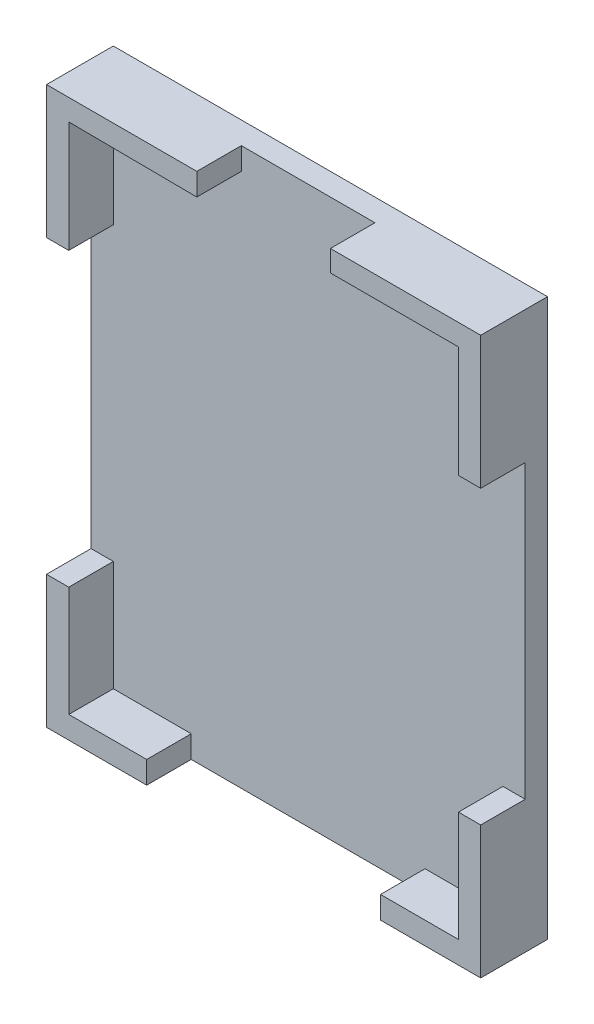
SolidWorks part; units mm, degrees
ref_plane "Front Plane" through (0, 0, 0) normal (0, 0, 1) x (1, 0, 0)
ref_plane "Top Plane" through (0, 0, 0) normal (0, 1, 0) x (1, 0, 0)
ref_plane "Right Plane" through (0, 0, 0) normal (1, 0, 0) x (0, 0, -1)
sketch "Sketch1" plane through (0, 0, 0) normal (0, 0, 1) x (1, 0, 0)
  line L5 (0, 50) -> (13.5, 50)
  line L8 (13.5, 50) -> (13.5, 48)
  line L9 (2, 48.0947) -> (13.5, 48)
  line L14 (37, 2) -> (30, 2)
  line L19 (37, 48.0947) -> (37, 38.0947)
  line L20 (39, 38.0947) -> (37, 38.0947)
  line L21 (39, 50) -> (39, 38.0947)
  line L22 (39, 0) -> (39, 11.9053)
  line L23 (39, 11.9053) -> (37, 11.9053)
  line L24 (37, 2) -> (37, 11.9053)
  line L35 (39, 0) -> (30, 0)
  line L36 (30, 0) -> (30, 2)
  line L37 (2, 38.0947) -> (0, 38.0947)
  line L42 (0, 0) -> (0, 11.9053)
  line L43 (0, 11.9053) -> (2, 11.9053)
  line L44 (2, 2) -> (2, 11.9053)
  line L45 (2, 2) -> (9, 2)
  line L46 (9, 0) -> (9, 2)
  line L47 (0, 0) -> (9, 0)
  line L48 (37, 48.0947) -> (25.5, 48.0947)
  line L49 (25.5, 48.0947) -> (25.5, 50)
  line L50 (25.5, 50) -> (39, 50)
  line L51 (0, 0) -> (39, 0)
  line L52 (0, 0) -> (0, 50)
  line L53 (0, 50) -> (39, 50)
  line L54 (39, 0) -> (39, 50)
  line L55 (0, 38.0947) -> (0, 50)
  line L56 (2, 48.0947) -> (2, 38.0947)
  dimension "D1" = 39
  dimension "D2" = 50
  dimension "D3" = 2
  dimension "D5" = 2
  dimension "D7" = 7
  dimension "D8" = 11.5
  dimension "D9" = 11.5
extrude "Boss-Extrude1" add sketch "Sketch1" along normal blind 2 contours L9 L8 | L20 L48 L19 | L23 L24 | L44 L45 L46 | L46 L45 L44 L24 L23 L20 L19 L48 L8 L9 region at (6.75, 49.82, 0) region at (19.503, 24.7788, 0) region at (32.25, 49.82, 0) region at (1, 11.756, 0) region at (38.8508, 5.9526, 0)
extrude "Boss-Extrude2" add sketch "Sketch1<4>" along normal blind 6 contours L9 L8 | L20 L48 L19 | L23 L24 | L44 L45 L46 region at (6.75, 49.82, 0) region at (32.25, 49.82, 0) region at (1, 11.756, 0) region at (38.8508, 5.9526, 0)
sketch "Sketch1<4>" plane through (0, 0, 0) normal (0, 0, 1) x (1, 0, 0) same geometry as "Sketch1"
